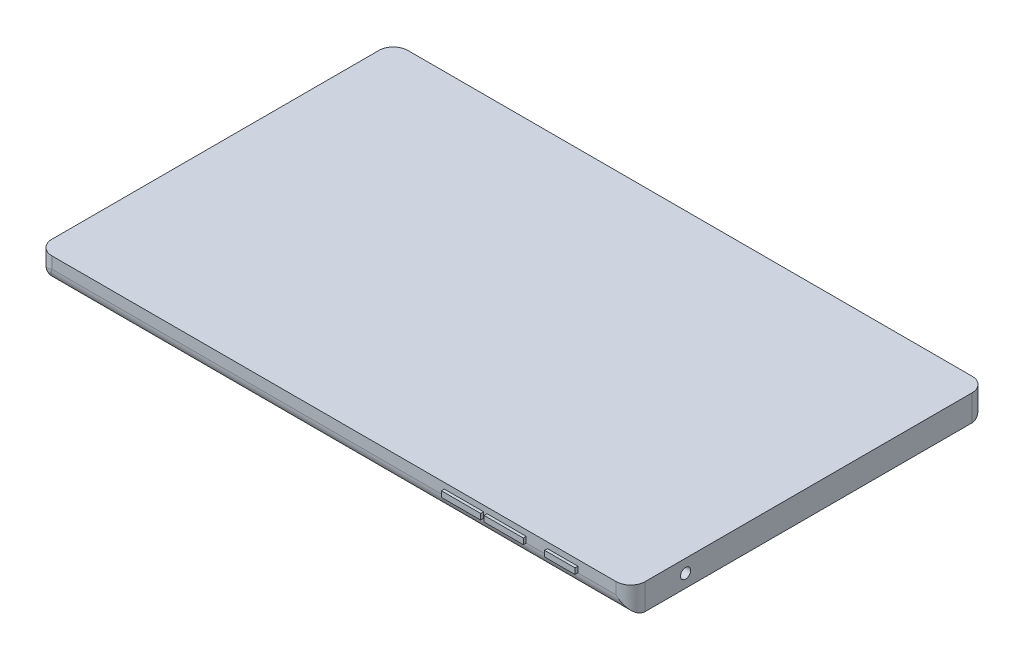
SolidWorks part; units mm, degrees
ref_plane "Front Plane" through (0, 0, 0) normal (0, 0, 1) x (1, 0, 0)
ref_plane "Top Plane" through (0, 0, 0) normal (0, 1, 0) x (1, 0, 0)
ref_plane "Right Plane" through (0, 0, 0) normal (1, 0, 0) x (0, 0, -1)
sketch "Sketch1" plane through (0, 0, 0) normal (0, 1, 0) x (1, 0, 0)
  line L1 (0, 0) -> (205, 0)
  line L2 (0, 0) -> (0, 123)
  line L3 (0, 123) -> (205, 123)
  line L4 (205, 0) -> (205, 123)
  dimension "D1" = 205
  dimension "D2" = 123
extrude "Boss-Extrude1" add sketch "Sketch1" along normal blind 9
sketch "Sketch3" plane through (205, 0, 0) normal (1, 0, 0) x (0, 0, -1)
  line L0 (19, 4.5) -> (0, 4.5)
  line L2 (0, 9) -> (0, 0) construction
  circle A0 centre (19, 4.5) radius 1.75
  point P2 (0, 0)
  point P3 (0, 0)
  point P5 (0, 5.3671)
  point P7 (0, 4.5)
  point P8 (0, 4.5)
  dimension "D1" = 3.5
  dimension "D2" = 19
fillet "Fillet1" radius 3 1 edges at (0, 0, -61.5)
fillet "Fillet2" radius 5 8 edges at (0, 6, -123) (0.8787, 0.8787, -123) (0, 6, 0) (0.8787, 0.8787, 0) (104, 0, -123) (104, 0, 0) (205, 4.5, -123) (205, 4.5, 0)
sketch "Sketch2" plane through (0, 0, 0) normal (-1, 0, 0) x (0, 0, 1)
  line L0 (-61.5, 9) -> (-61.5, 3) construction
  line L1 (-118, 9) -> (-5, 9) construction
  line L3 (-118, 3) -> (-5, 3) construction
  line L5 (-57.75, 7.1741) -> (-65.25, 7.1741)
  line L6 (-57.75, 7.1741) -> (-57.75, 4.1596)
  line L7 (-57.75, 4.1596) -> (-65.25, 4.1596)
  line L8 (-65.25, 7.1741) -> (-65.25, 4.1596)
  point P4 (-61.5, 4.1596)
  dimension "D1" = 7.5
extrude "Cut-Extrude1" cut sketch "Sketch2" against normal blind 4
extrude "Cut-Extrude2" cut sketch "Sketch3" against normal blind 13.5 contours A0 region at (205, 2.7995, -19)
sketch "Sketch5" plane through (0, 0, 0) normal (0, 0, 1) x (1, 0, 0)
  line L0 (5, 5) -> (200, 5) construction
  line L1 (176.25, 7) -> (186.75, 7)
  line L2 (176.25, 7) -> (176.25, 5)
  line L3 (176.25, 5) -> (186.75, 5)
  line L4 (186.75, 7) -> (186.75, 5)
  line L6 (205, 9) -> (205, 0) construction
  line L7 (154.765, 7) -> (154.765, 5) construction
  line L8 (168.92, 7) -> (140.61, 7)
  line L9 (168.92, 7) -> (168.92, 5)
  line L10 (168.92, 5) -> (140.61, 5)
  line L11 (140.61, 7) -> (140.61, 5)
  line L13 (155.3609, 5) -> (154.1691, 5)
  line L14 (155.3609, 5) -> (155.3609, 7)
  line L15 (155.3609, 7) -> (154.1691, 7)
  line L16 (154.1691, 5) -> (154.1691, 7)
  point P12 (168.92, 6)
  line M6 (5, 5) -> (200, 5)
  dimension "D1" = 18.25
  dimension "D2" = 10.5
  dimension "D3" = 17.83
  dimension "D4" = 28.31
  dimension "D5" = 2
  dimension "D6" = 2
extrude "Boss-Extrude2" add sketch "Sketch5" along normal blind 1 contours L4 L1 L2 M6 | L14 L9 L8 M6 | L16 L8 L11 M6 region at (162.1404, 6, 0) region at (181.5, 6, 0) region at (147.3896, 6, 0)
